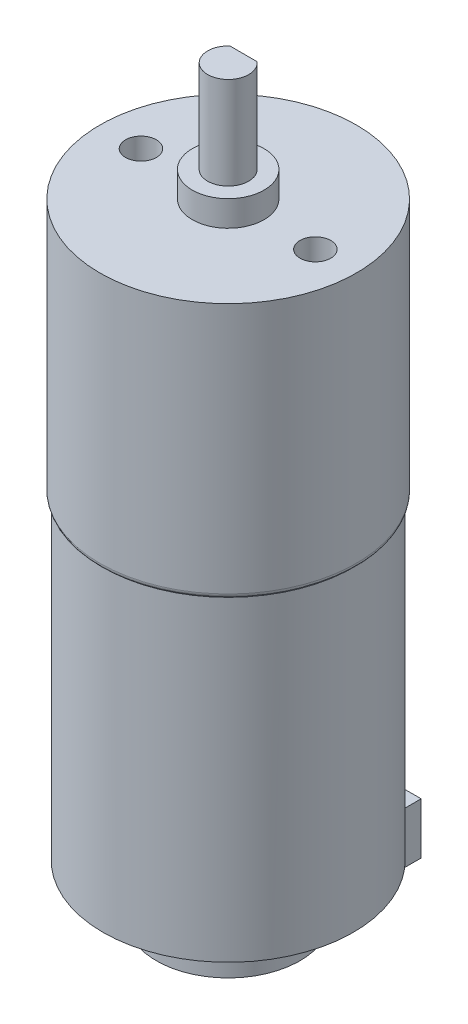
SolidWorks part; units mm, degrees
ref_plane "Front Plane" through (0, 0, 0) normal (0, 0, 1) x (1, 0, 0)
ref_plane "Top Plane" through (0, 0, 0) normal (0, 1, 0) x (1, 0, 0)
ref_plane "Right Plane" through (0, 0, 0) normal (1, 0, 0) x (0, 0, -1)
sketch "Sketch1" plane through (0, 0, 0) normal (0, 1, 0) x (1, 0, 0)
  circle A0 centre (0, 0) radius 12.5
extrude "Boss-Extrude1" add sketch "Sketch1" along normal blind 25 contours A0
fillet "Fillet1" radius 0.5 1 edges at (0, 0, 12.5) type face fillet first side face at (0, 0, 12.5) second side face at (0, 25, 12.5)
sketch "Sketch3" plane through (0, 0, 0) normal (0, -1, 0) x (1, 0, 0)
  circle A0 centre (0, 0) radius 12.2
extrude "Boss-Extrude2" add sketch "Sketch3" along normal blind 30.8
sketch "Sketch4" plane through (0, 25, 0) normal (0, 1, 0) x (1, 0, 0)
  circle A0 centre (0, 0) radius 3.5
extrude "Boss-Extrude3" add sketch "Sketch4" along normal blind 2.5
sketch "Sketch5" plane through (0, 27.5, 0) normal (0, 1, 0) x (1, 0, 0)
  circle A0 centre (0, 0) radius 2
extrude "Boss-Extrude4" add sketch "Sketch5" along normal blind 9
sketch "Sketch6" plane through (0, 36.5, 0) normal (0, 1, 0) x (1, 0, 0)
  line L0 (0, 0) -> (0, 1.5) construction
  line L1 (1.3229, 1.5) -> (-1.3229, 1.5)
  circle A1 centre (0, 0) radius 2 construction
  arc A2 (-1.3229, 1.5) -> (1.3229, 1.5) centre (0, 0) cw
extrude "Cut-Extrude1" cut sketch "Sketch6" against normal blind 8
sketch "Sketch7" plane through (0, 25, 0) normal (0, 1, 0) x (1, 0, 0)
  line L0 (-8.5, 0) -> (8.5, 0) construction
  circle A0 centre (-8.5, 0) radius 1.5
  circle A1 centre (8.5, 0) radius 1.5
  point P6 (0, 0)
extrude "Cut-Extrude2" cut sketch "Sketch7" against normal blind 5
sketch "Sketch8" plane through (0, -30.8, 0) normal (0, -1, 0) x (1, 0, 0)
  line L0 (0, 0) -> (0, -12.5) construction
  line L2 (-4.2266, -14.5799) -> (4.2266, -14.5799)
  line L3 (-4.2266, -14.5799) -> (-4.2266, -10.4201)
  line L4 (-4.2266, -10.4201) -> (4.2266, -10.4201)
  line L5 (4.2266, -14.5799) -> (4.2266, -10.4201)
  line L6 (-4.2266, -14.5799) -> (4.2266, -10.4201) construction
  line L7 (-4.2266, -10.4201) -> (4.2266, -14.5799) construction
  circle A0 centre (0, 0) radius 7
  circle A1 centre (0, 0) radius 12.5 construction
extrude "Boss-Extrude5" add sketch "Sketch8" along normal blind 5
